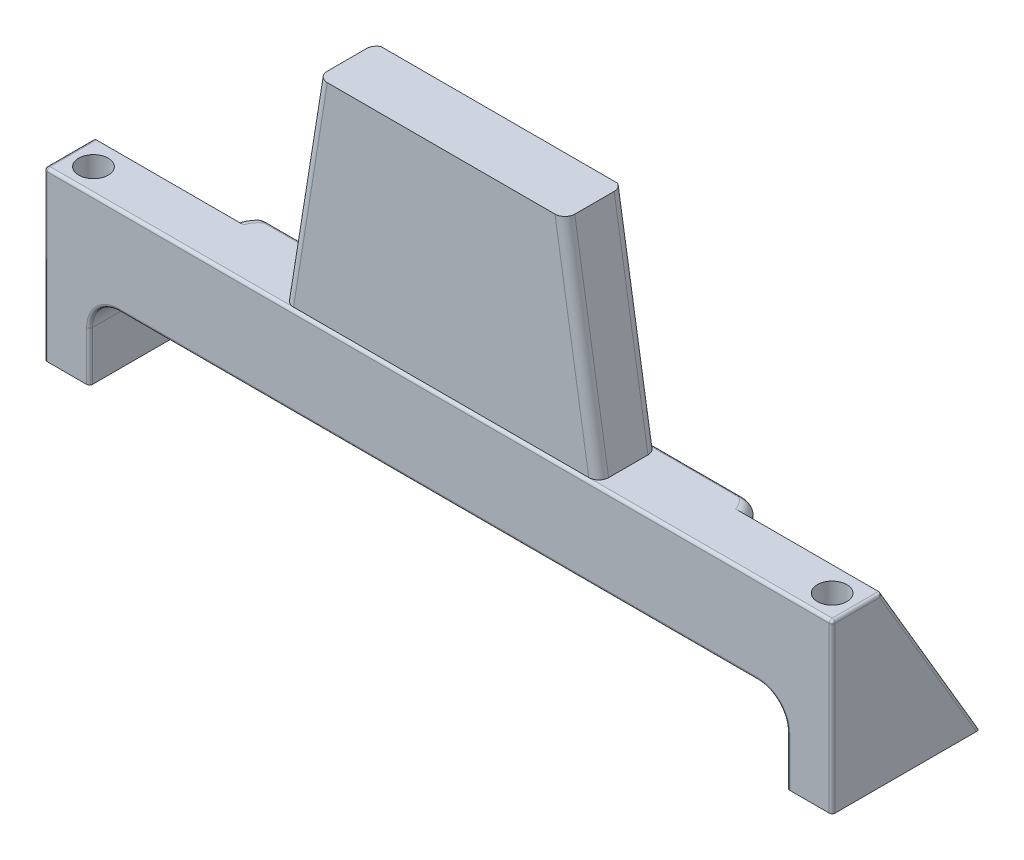
SolidWorks part; units mm, degrees
other "标注1"
sketch "草图3" plane through (-40, -10, 5) normal (0, 0, 1) x (1, 0, 0)
other "标注3"
sketch "草图14" plane through (-40, -10, 4) normal (0, 0, 1) x (1, 0, 0)
other "标注4"
sketch "草图17" plane through (-40, 10, 4) normal (-0.7745, 0.483, 0.4085) x (0.5245, 0.1294, 0.8415)
ref_plane "前视基准面" through (0, 0, 0) normal (0, 0, 1) x (1, 0, 0)
ref_plane "上视基准面" through (0, 0, 0) normal (0, 1, 0) x (1, 0, 0)
ref_plane "右视基准面" through (0, 0, 0) normal (1, 0, 0) x (0, 0, -1)
sketch "草图1" plane through (0, 0, 0) normal (0, 0, 1) x (1, 0, 0)
  line L1 (-40, -10) -> (40, -10)
  line L2 (-40, -10) -> (-40, 10)
  line L3 (-40, 10) -> (40, 10)
  line L4 (40, -10) -> (40, 10)
  line L5 (-40, -10) -> (40, 10) construction
  line L6 (-40, 10) -> (40, -10) construction
  point P0 (0, 0)
extrude "凸台-拉伸3" add sketch "草图1" along normal blind 4
sketch "草图5" plane through (0, 10, 0) normal (0, 1, 0) x (1, 0, 0)
  line L0 (0, -2.7482) -> (0, 2.7482) construction
  circle A0 centre (37.5, -2) radius 1.5
  circle A1 centre (-37.5, -2) radius 1.5
sketch "草图7" plane through (0, 0, 4) normal (0, 0, 1) x (1, 0, 0)
  line L0 (-35.4, -2) -> (-35.4, -10)
  line L3 (-35.4, -2) -> (35.4, -2)
  line L4 (-40, -10) -> (40, -10) construction
  line L6 (35.4, -2) -> (35.4, -10)
  line L7 (-35.4, -10) -> (35.4, -10)
extrude "凸台-拉伸5" add sketch "草图1<3>" against normal blind 0.5 and the other way blind 4.4967
sketch "草图1<3>" plane through (0, 0, 0) normal (0, 0, 1) x (1, 0, 0) same geometry as "草图1"
extrude "切除-拉伸7" cut sketch "草图5" against normal through all
sketch "草图18" plane through (0, 10, 0) normal (0, 1, 0) x (1, 0, 0)
  line L1 (-40, 0.5) -> (40, 0.5)
  line L2 (-40, 0.5) -> (-40, -4.4967)
  line L3 (-40, -4.4967) -> (40, -4.4967)
  line L4 (40, 0.5) -> (40, -4.4967)
extrude "切除-拉伸9" cut sketch "草图18" against normal blind 3
extrude "切除-拉伸12" cut sketch "草图7" against normal up to next and the other way through all
fillet "圆角3" radius 3 1 edges at (35.4, -2, 1.9984)
fillet "圆角5" radius 3 1 edges at (-35.4, -2, 1.9984)
sketch "草图19" plane through (0, 0, -0.5) normal (0, 0, -1) x (-1, 0, 0)
  line L1 (40, 7) -> (35.4, 7)
  line L2 (40, 7) -> (40, -10)
  line L3 (40, -10) -> (35.4, -10)
  line L4 (35.4, 7) -> (35.4, -10)
  line L5 (-40, 7) -> (-35.4, 7)
  line L6 (-40, 7) -> (-40, -10)
  line L7 (-40, -10) -> (-35.4, -10)
  line L8 (-35.4, 7) -> (-35.4, -10)
extrude "凸台-拉伸6" add sketch "草图19" along normal blind 10
sketch "草图20" plane through (-35.4, 0, 0) normal (1, 0, 0) x (0, 0, -1)
  line L0 (10.5, -10) -> (10.5, 7)
  line L1 (10.5, 7) -> (0.5, 7)
  line L2 (0.5, 7) -> (10.5, -10)
extrude "切除-拉伸13" cut sketch "草图20" against normal mid plane 100000
sketch "草图21" plane through (0, 0, -0.5) normal (0, 0, -1) x (-1, 0, 0)
  line L0 (-35.4, 7) -> (35.4, 7) construction
  line L1 (-26.2107, 7) -> (25.7738, 7)
  line L2 (-26.2107, 7) -> (-26.2107, -2)
  line L3 (-26.2107, -2) -> (25.7738, -2)
  line L4 (25.7738, 7) -> (25.7738, -2)
  line L5 (-32.4, -2) -> (32.4, -2) construction
extrude "凸台-拉伸8" add sketch "草图21" along normal blind 2.5
fillet "圆角8" radius 3 1 edges at (26.2107, 2.5, -3)
fillet "圆角9" radius 3 1 edges at (-25.7738, 2.5, -3)
fillet "圆角10" radius 1 3 edges at (-24.7523, 7, -2.2913) (25.1891, 7, -2.2913) (0.2184, 7, -3)
fillet "圆角13" radius 0.3 3 edges at (0, 7, 4.4967) (-40, -1.5, 4.4967) (-40, 7, 1.9984)
fillet "圆角14" radius 0.3 4 edges at (40, -1.65, 4.4967) (40, 6.9121, 4.4088) (40, -1.5, -5.5) (40, 7, 1.8484)
fillet "圆角15" radius 0.3 2 edges at (-35.4, -1.5, -5.5) (35.4, -1.5, -5.5)
fillet "圆角18" radius 0.3 5 edges at (35.4, -7.5, 4.4967) (34.5213, -2.8787, 4.4967) (-35.4, -7.5, 4.4967) (-34.5213, -2.8787, 4.4967) (0, -2, 4.4967)
sketch "草图22" plane through (0, 0, -3) normal (0, 0, -1) x (-1, 0, 0)
  line L0 (24.7523, 7) -> (35.7, 7) construction
  line L1 (-26.2107, -2) -> (25.7983, -2)
  line L2 (-26.2107, -2) -> (-26.2107, 7)
  line L3 (-26.2107, 7) -> (25.7983, 7)
  line L4 (25.7983, -2) -> (25.7983, 7)
extrude "切除-拉伸14" cut sketch "草图22" against normal blind 1
fillet "圆角19" radius 0.3 5 edges at (-25.0519, 2, -2) (-20.8232, 5.4322, -2) (0.2184, 7, -2) (21.6435, 5.1763, -2) (25.4887, 2, -2)
sketch "草图23" plane through (0, 0, 4.4967) normal (0, 0, 1) x (1, 0, 0)
  point P4 (0, 0)
sketch "草图25" plane through (0, 7, 0) normal (0, 1, 0) x (1, 0, 0)
  line L1 (-12, 1.7) -> (12, 1.7)
  line L2 (24.3062, 1.7) -> (-23.8694, 1.7) construction
  line L3 (12, 1.7) -> (12, -4.1967)
  line L4 (-39.7, -4.1967) -> (39.7, -4.1967) construction
  line L5 (12, -4.1967) -> (-12, -4.1967)
  line L6 (-12, -4.1967) -> (-12, 1.7)
  point P4 (0, 0)
extrude "凸台-拉伸10" add sketch "草图25" along normal blind 25
sketch "草图27" plane through (0, 0, 4.1967) normal (0, 0, 1) x (1, 0, 0)
  line L0 (12, 32) -> (16, 7)
  line L1 (12, 7) -> (39.7, 7) construction
  line L2 (16, 7) -> (12, 7)
  line L3 (12, 7) -> (12, 32)
  line L4 (0, -8.2482) -> (0, 8.2482) construction
  line L5 (-12, 7) -> (-12, 32)
  line L6 (-16, 7) -> (-12, 7)
  line L7 (-12, 32) -> (-16, 7)
  point P5 (12, 32)
extrude "凸台-拉伸12" add sketch "草图27" against normal blind 6
fillet "圆角22" radius 1 6 edges at (0, 32, -1.7) (14, 19.5, -1.8033) (-14, 19.5, -1.8033) (-14, 19.5, 4.1967) (14, 19.5, 4.1967) (0, 32, 4.1967)
sketch "草图28" plane through (0, 0, 4.1967) normal (0, 0, 1) x (1, 0, 0)
  line L0 (-12, 32) -> (-12.567, 28.4562)
  line L1 (-16, 7) -> (-12, 32) construction
  line L2 (-12.567, 28.4562) -> (12.567, 28.4562)
  line L3 (12, 32) -> (16, 7) construction
  line L4 (12.567, 28.4562) -> (12, 32)
  line L5 (12, 32) -> (-12, 32)
extrude "切除-拉伸15" cut sketch "草图28" against normal blind 25
